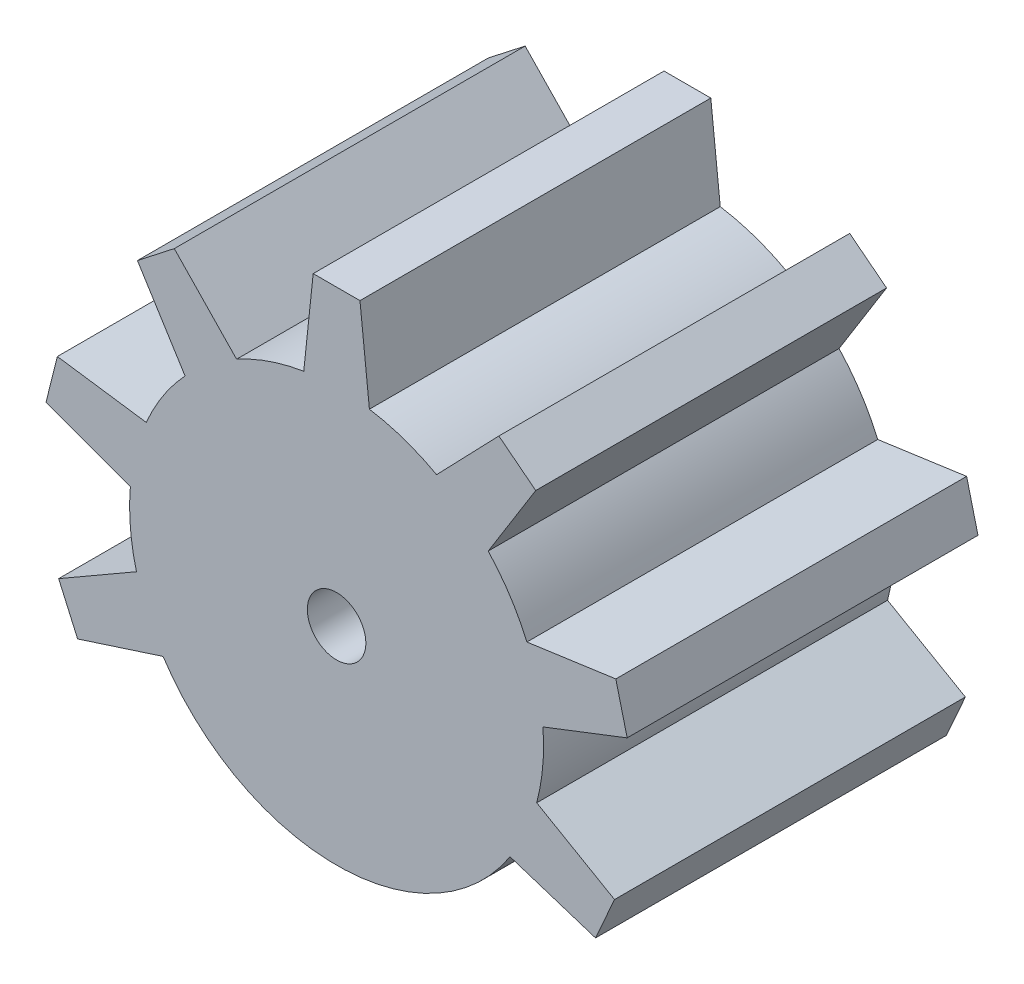
SolidWorks part; units mm, degrees
ref_plane "Спереди" through (0, 0, 0) normal (0, 0, 1) x (1, 0, 0)
ref_plane "Сверху" through (0, 0, 0) normal (0, 1, 0) x (1, 0, 0)
ref_plane "Справа" through (0, 0, 0) normal (1, 0, 0) x (0, 0, -1)
sketch "Эскиз3" plane through (0, 0, 0) normal (0, 0, 1) x (1, 0, 0)
  point P0 (0, 0)
  line B0 (0, 12.5567) -> (0, -11.4003) construction
  line B1 (-17.4471, 0) -> (17.8457, 0) construction
  line B2 (-1, 12.5567) -> (0, 12.5567)
  line B3 (0, 12.5567) -> (1, 12.5567)
  line B4 (-8.5148, 9.2827) -> (-6.9383, 10.5133)
  line B5 (-12.4239, 2.0778) -> (-11.9384, 4.018)
  line B6 (6.9383, 10.5133) -> (8.5148, 9.2827)
  line B7 (-11.883, -4.1789) -> (-11.0719, -6.007)
  line B8 (11.9384, 4.018) -> (12.4239, 2.0778)
  line B9 (11.0719, -6.007) -> (11.883, -4.1789)
  line B10 (-6.4791, 6.0286) -> (-8.5148, 9.2827)
  line B11 (-4.2757, 7.7486) -> (-6.9383, 10.5133)
  line B12 (-8.1384, 3.477) -> (-11.9384, 4.018)
  line B13 (-12.4239, 2.0778) -> (-8.8168, 0.7654)
  line B14 (-11.883, -4.1789) -> (-8.5563, -2.261)
  line B15 (-11.0719, -6.007) -> (-7.4176, -4.8272)
  line B16 (-1, 12.5567) -> (-1.4038, 8.738)
  line B17 (1, 12.5567) -> (1.4038, 8.738)
  line B18 (6.9383, 10.5133) -> (4.2757, 7.7486)
  line B19 (8.5148, 9.2827) -> (6.4833, 6.0241)
  line B20 (11.9384, 4.018) -> (8.1359, 3.4827)
  line B21 (12.4239, 2.0778) -> (8.8236, 0.6833)
  line B22 (11.883, -4.1789) -> (8.5563, -2.261)
  line B23 (11.0719, -6.007) -> (7.4176, -4.8272)
  arc B24 (-8.5563, -2.261) -> (-8.8168, 0.7654) centre (0, 0) cw
  arc B25 (-7.4176, -4.8272) -> (7.4176, -4.8272) centre (0, 0) ccw
  arc B26 (-8.1384, 3.477) -> (-6.4791, 6.0286) centre (0, 0) cw
  arc B27 (-4.2757, 7.7486) -> (-1.4038, 8.738) centre (0, 0) cw
  arc B28 (1.4038, 8.738) -> (4.2757, 7.7486) centre (0, 0) cw
  arc B29 (6.4833, 6.0241) -> (8.1359, 3.4827) centre (0, 0) cw
  arc B30 (8.8236, 0.6833) -> (8.5563, -2.261) centre (0, 0) cw
sketch_block_instance "Блок1-1"
sketch_block "Блок1"
extrude "Бобышка-Вытянуть2" add sketch "Эскиз3" along normal blind 15
sketch "Эскиз5" plane through (0, 0, 0) normal (0, 0, -1) x (-1, 0, 0)
  circle A0 centre (0, 0) radius 1.25
extrude "Вырез-Вытянуть1" cut sketch "Эскиз5" against normal blind 15
sketch "Эскиз7" plane through (0, 0, 15) normal (0, 0, 1) x (1, 0, 0)
  line L0 (0, 0) -> (0, 12.5567)
  line L1 (1, 12.5567) -> (-1, 12.5567) construction
  line L2 (0, 8.85) -> (0, 12.5567)
  line L3 (0, 12.5567) -> (-3.0001, 12.2653)
  circle A0 centre (0, 0) radius 8.85
